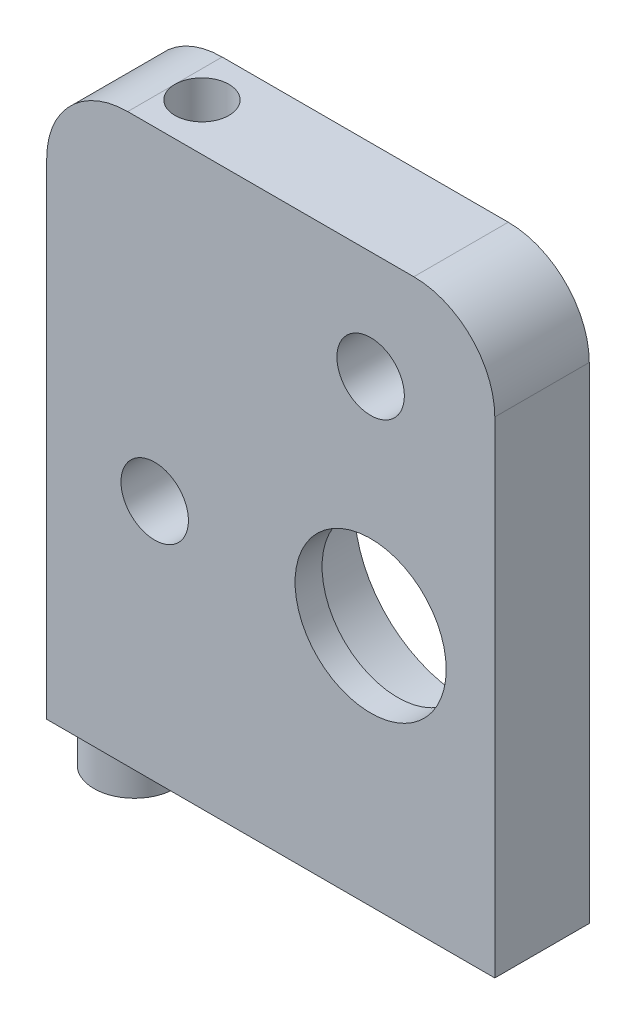
SolidWorks part; units mm, degrees
ref_plane "前视基准面" through (0, 0, 0) normal (0, 0, 1) x (1, 0, 0)
ref_plane "上视基准面" through (0, 0, 0) normal (0, 1, 0) x (1, 0, 0)
ref_plane "右视基准面" through (0, 0, 0) normal (1, 0, 0) x (0, 0, -1)
other "Configuration Table"
sketch "草图1" plane through (0, 0, 0) normal (0, 0, 1) x (1, 0, 0)
  line L1 (-12, 12) -> (4.6, 12)
  line L2 (-12, 12) -> (-12, -9)
  line L3 (-12, -9) -> (4.6, -9)
  line L4 (4.6, 12) -> (4.6, -9)
  circle A0 centre (0, 0) radius 2.8
  circle A1 centre (0, 0) radius 4.1
  circle A2 centre (0, 8) radius 1.25
  circle A3 centre (-8, 0) radius 1.25
  dimension "D1" = 5.6
  dimension "D2" = 8.2
  dimension "D7" = 2.5
  dimension "D9" = 2.5
  dimension "D3" = 12
  dimension "D4" = 12
  dimension "D5" = 9
  dimension "D6" = 4.6
  dimension "D8" = 8
  dimension "D10" = 8
extrude "凸台-拉伸1" add sketch "草图1" along normal blind 3.5 contours L4 L1 L2 L3 A3 A2 A1 region at (-4.373, 1.6912, 0)
extrude "凸台-拉伸2" add sketch "草图1<3>" against normal blind 1 from surface contours A1 A0 region at (-3.984, 0, 0) starting at face at (-6.75, 0, 3.5)
sketch "草图1<3>" plane through (0, 0, 0) normal (0, 0, 1) x (1, 0, 0) same geometry as "草图1"
fillet "圆角1" radius 3 1 edges at (-12, 12, 1.75)
fillet "圆角2" radius 3 1 edges at (4.6, 12, 1.75)
sketch "草图2" plane through (0, -9, 0) normal (0, -1, 0) x (1, 0, 0)
  line L0 (-12, 0) -> (4.6, 0) construction
  line L3 (-12, 3.5) -> (-12, 0) construction
  circle A0 centre (-10.5, 1.75) radius 1.5
  circle A2 centre (-4.5, 1.75) radius 1
  dimension "D1" = 3
  dimension "D3" = 4.5
  dimension "D4" = 2
  dimension "D2" = 1.75
  dimension "D5" = 6
extrude "切除-拉伸1" cut sketch "草图2" against normal blind 6 contours A2 region at (-4.5, -9, 1.75)
extrude "凸台-拉伸3" add sketch "草图2<3>" along normal blind 1.6 contours A0 region at (-10.5, -9, 1.75)
sketch "草图2<3>" plane through (0, -9, 0) normal (0, -1, 0) x (1, 0, 0) same geometry as "草图2"
sketch "草图4" plane through (0, 12, 0) normal (0, 1, 0) x (1, 0, 0)
  line L0 (-9, 0) -> (1.6, 0) construction
  circle A0 centre (-8, -1.75) radius 1
  dimension "D2" = 2
  dimension "D1" = 8
  dimension "D3" = 1.75
extrude "切除-拉伸2" cut sketch "草图4" against normal blind 6
